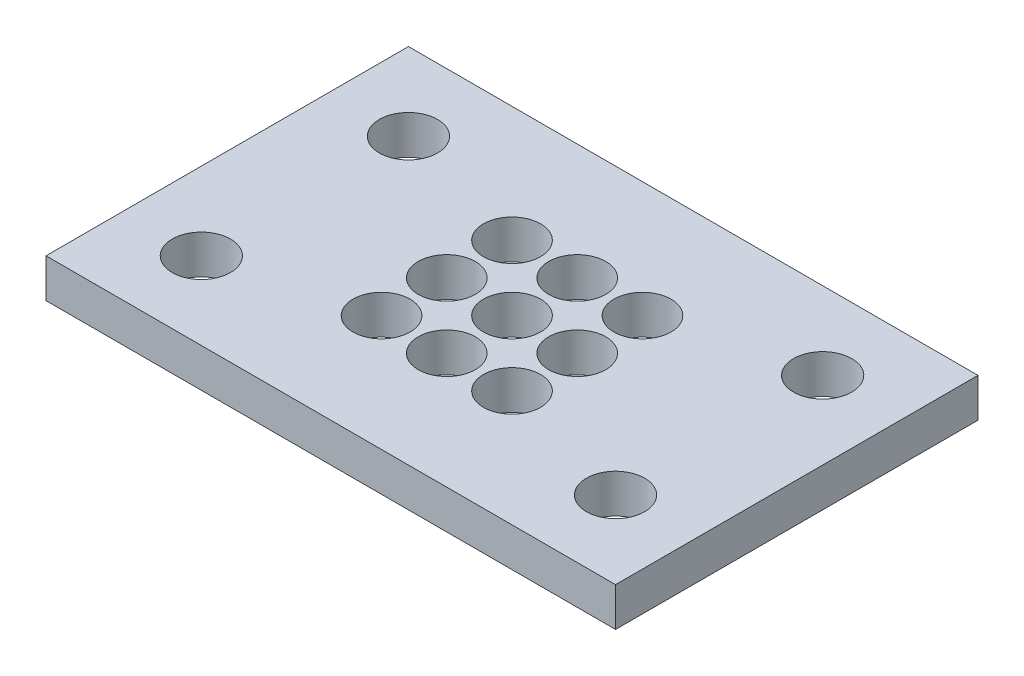
SolidWorks part; units mm, degrees
ref_plane "Front Plane" through (0, 0, 0) normal (0, 0, 1) x (1, 0, 0)
ref_plane "Top Plane" through (0, 0, 0) normal (0, 1, 0) x (1, 0, 0)
ref_plane "Right Plane" through (0, 0, 0) normal (1, 0, 0) x (0, 0, -1)
sketch "Sketch1" plane through (0, 0, 0) normal (0, 1, 0) x (1, 0, 0)
  line L0 (9.525, 34.925) -> (0, 34.925) construction
  line L1 (0, 0) -> (69.85, 0)
  line L2 (0, 0) -> (0, 44.45)
  line L3 (0, 44.45) -> (69.85, 44.45)
  line L4 (69.85, 0) -> (69.85, 44.45)
  line L5 (9.525, 34.925) -> (60.325, 34.925) construction
  line L6 (9.525, 34.925) -> (9.525, 9.525) construction
  line L7 (9.525, 9.525) -> (60.325, 9.525) construction
  line L8 (60.325, 34.925) -> (60.325, 9.525) construction
  line L9 (9.525, 34.925) -> (9.525, 44.45) construction
  circle A0 centre (9.525, 34.925) radius 3.5687
  circle A1 centre (60.325, 34.925) radius 3.5687
  circle A2 centre (9.525, 9.525) radius 3.5687
  circle A3 centre (60.325, 9.525) radius 3.5687
  circle A4 centre (34.925, 22.225) radius 3.5
  circle A5 centre (42.925, 22.225) radius 3.5
  circle A6 centre (42.925, 30.225) radius 3.5
  circle A7 centre (34.925, 30.225) radius 3.5
  circle A8 centre (26.925, 22.225) radius 3.5
  circle A9 centre (26.925, 30.225) radius 3.5
  circle A10 centre (34.925, 30.225) radius 3.5
  circle A11 centre (26.925, 22.225) radius 3.5
  circle A12 centre (26.925, 14.225) radius 3.5
  circle A13 centre (34.925, 14.225) radius 3.5
  circle A14 centre (42.925, 22.225) radius 3.5
  circle A15 centre (42.925, 14.225) radius 3.5
  circle A16 centre (34.925, 14.225) radius 3.5
  point P13 (34.925, 34.925)
  point P14 (34.925, 44.45)
  point P20 (69.85, 22.225)
  dimension "D5" = 7.1374
  dimension "D6" = 7
  dimension "D1" = 69.85
  dimension "D2" = 44.45
  dimension "D3" = 50.8
  dimension "D4" = 25.4
  dimension "D7" = 2
  dimension "D8" = 2
  dimension "D9" = 2
  dimension "D10" = 2
  dimension "D11" = 2
  dimension "D12" = 2
  dimension "D13" = 2
  dimension "D14" = 2
extrude "Boss-Extrude1" add sketch "Sketch1" along normal blind 4.7625 contours L1 L4 L3 L2 A15 A13 A12 A9 A8 A7 A6 A5 A4 A3 A2 A1 A0 region at (0.8279, 0, -22.225)
